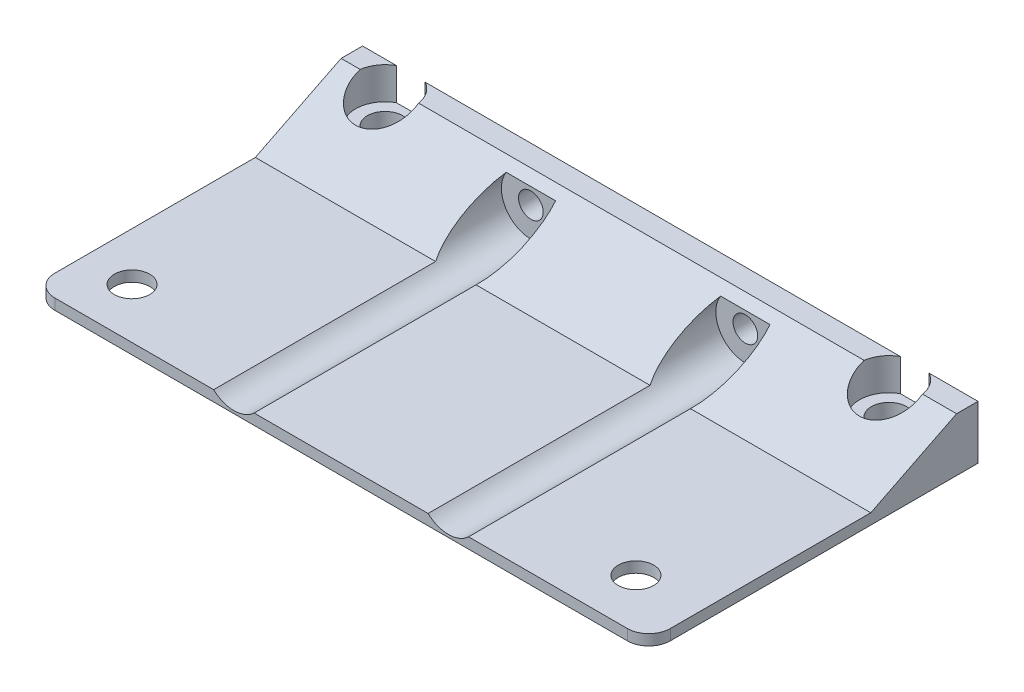
SolidWorks part; units mm, degrees
ref_plane "Front Plane" through (0, 0, 0) normal (0, 0, 1) x (1, 0, 0)
ref_plane "Top Plane" through (0, 0, 0) normal (0, 1, 0) x (1, 0, 0)
ref_plane "Right Plane" through (0, 0, 0) normal (1, 0, 0) x (0, 0, -1)
sketch "Sketch1" plane through (0, 0, 0) normal (0, 1, 0) x (1, 0, 0)
  line L0 (4.5, 28.3) -> (4.5, 4.7) construction
  line L1 (0, 0) -> (57.4, 0)
  line L2 (0, 0) -> (0, 33)
  line L3 (0, 33) -> (57.4, 33)
  line L4 (57.4, 0) -> (57.4, 33)
  circle A0 centre (4.5, 28.3) radius 1.65
  circle A1 centre (51.5, 28.3) radius 1.65
  circle A2 centre (4.5, 4.7) radius 1.65
  circle A3 centre (51.5, 4.7) radius 1.65
  point P13 (0, 16.5)
  point P14 (4.5, 16.5)
  dimension "D3" = 3.3
  dimension "D4" = 47
  dimension "D5" = 23.6
  dimension "D6" = 4.5
  dimension "D1" = 57.4
  dimension "D2" = 33
extrude "Boss-Extrude1" add sketch "Sketch1" along normal blind 1
sketch "Sketch2" plane through (0, 1, 0) normal (0, 1, 0) x (1, 0, 0)
  line L0 (57.4, 0) -> (57.4, 33) construction
  line L1 (0, 33) -> (57.4, 33)
  line L2 (0, 33) -> (0, 30.7)
  line L3 (0, 30.7) -> (57.4, 30.7)
  line L4 (57.4, 33) -> (57.4, 30.7)
  dimension "D1" = 2.3
extrude "Cut-Extrude1" cut sketch "Sketch2" against normal up to next
sketch "Sketch3" plane through (57.4, 0, 0) normal (1, 0, 0) x (0, 0, -1)
  line L0 (30.7, 1) -> (30.7, 5)
  line L1 (30.7, 5) -> (28.7, 5)
  line L2 (28.7, 5) -> (20.7, 1)
  line L3 (0, 1) -> (30.7, 1) construction
  line L4 (20.7, 1) -> (30.7, 1)
  dimension "D1" = 4
  dimension "D2" = 10
  dimension "D3" = 2
extrude "Boss-Extrude2" add sketch "Sketch3" against normal up to surface (57.4 mm away) up to face at (0, 0.5, -15.35)
fillet "Fillet1" radius 2 2 edges at (0, 0.5, 0) (57.4, 0.5, 0)
sketch "Sketch4" plane through (0, 0, 0) normal (0, -1, 0) x (-1, 0, 0)
  circle A0 centre (-4.5, 28.3) radius 1.65
  circle A1 centre (-51.5, 28.3) radius 1.65
  dimension "D1" = 3.3
extrude "Cut-Extrude2" cut sketch "Sketch4" against normal blind 2
sketch "Sketch5" plane through (0, 2, 0) normal (0, -1, 0) x (-1, 0, 0)
  circle A0 centre (-4.5, 28.3) radius 2.75
  circle A1 centre (-51.5, 28.3) radius 2.75
  dimension "D1" = 5.5
extrude "Cut-Extrude3" cut sketch "Sketch5" against normal up to next
sketch "Sketch6" plane through (0, 0, -30.7) normal (0, 0, -1) x (-1, 0, 0)
  circle A0 centre (-38.7, 3) radius 1.15
  circle A1 centre (-18.7, 3) radius 1.15
  dimension "D1" = 2.3
extrude "Cut-Extrude4" cut sketch "Sketch6" against normal blind 3
sketch "Sketch9" plane through (0, 0, -27.7) normal (0, 0, -1) x (-1, 0, 0)
  circle A0 centre (-38.7, 3) radius 2.75
  circle A1 centre (-18.7, 3) radius 2.75
  dimension "D1" = 5.5
extrude "Cut-Extrude5" cut sketch "Sketch9" against normal through all
